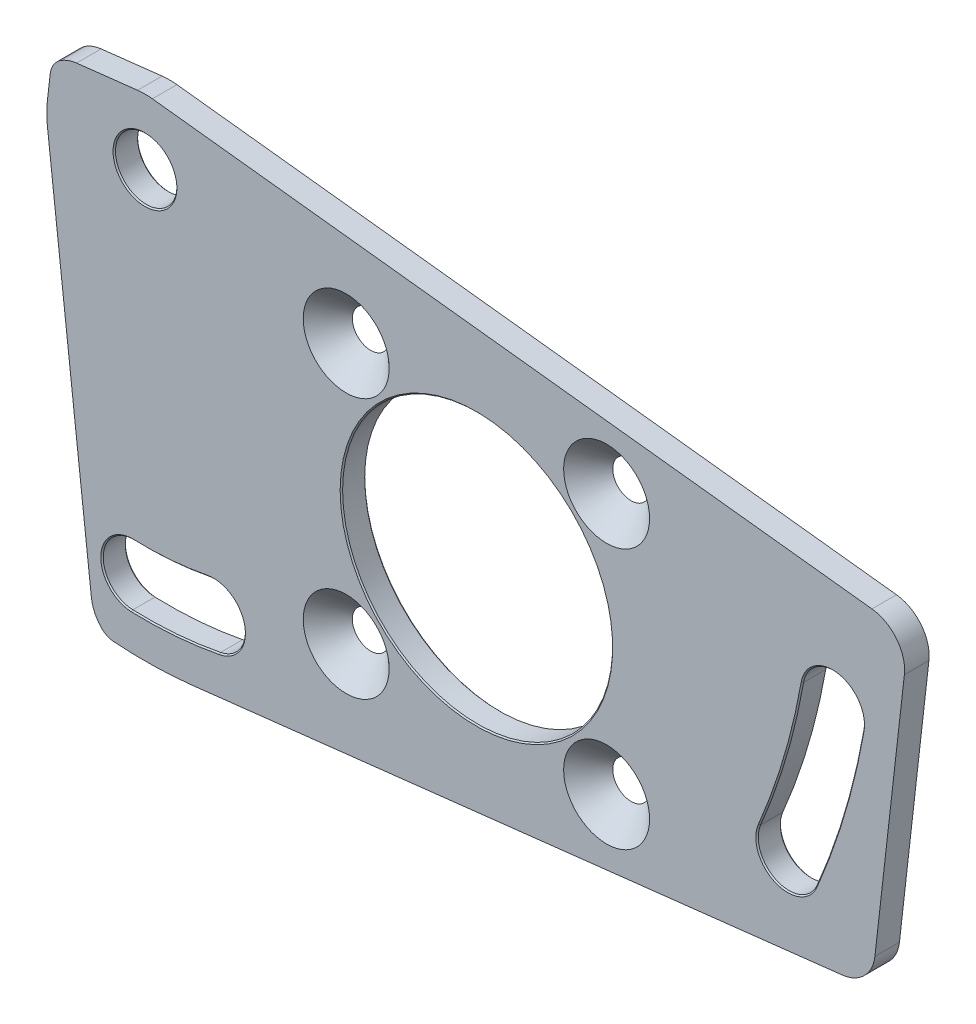
SolidWorks part; units mm, degrees
ref_plane "Płaszczyzna przednia" through (0, 0, 0) normal (0, 0, 1) x (1, 0, 0)
ref_plane "Płaszczyzna górna" through (0, 0, 0) normal (0, 1, 0) x (1, 0, 0)
ref_plane "Płaszczyzna prawa" through (0, 0, 0) normal (1, 0, 0) x (0, 0, -1)
sketch "Szkic1" plane through (0, 0, 0) normal (0, 0, 1) x (1, 0, 0)
  line L0 (25.3611, -7.5593) -> (-27, 14.6667) construction
  line L1 (-32, -20) -> (32, -20)
  line L2 (-35, -17) -> (-35, 17)
  line L3 (-32, 20) -> (32, 20)
  line L4 (35, -17) -> (35, 17)
  line L5 (-35, -20) -> (35, 20) construction
  line L6 (-35, 20) -> (35, -20) construction
  line L7 (-27, 14.6667) -> (29.0188, 4.789) construction
  line L10 (-28, -14.4829) -> (-27, 14.6667) construction
  line L11 (-27, 14.6667) -> (-21.4172, -13.9607) construction
  arc A0 (-32, -20) -> (-35, -17) centre (-32, -17) cw
  arc A1 (32, -20) -> (35, -17) centre (32, -17) ccw
  arc A2 (32, 20) -> (35, 17) centre (32, 17) cw
  arc A3 (-35, 17) -> (-32, 20) centre (-32, 17) cw
  circle A4 centre (0, 0) radius 11
  circle A5 centre (-27, 14.6667) radius 2.5
  arc A6 (25.3611, -7.5593) -> (29.0188, 4.789) centre (-27, 14.6667) ccw construction
  arc A7 (27.6623, -8.5361) -> (31.4808, 4.3549) centre (-27, 14.6667) ccw
  arc A8 (23.0598, -6.5825) -> (26.5568, 5.2232) centre (-27, 14.6667) ccw
  arc A9 (23.0598, -6.5825) -> (27.6623, -8.5361) centre (25.3611, -7.5593) ccw
  arc A10 (31.4808, 4.3549) -> (26.5568, 5.2232) centre (29.0188, 4.789) ccw
  arc A13 (-28, -14.4829) -> (-21.4172, -13.9607) centre (-27, 14.6667) ccw construction
  arc A14 (-28.0857, -16.9814) -> (-20.9386, -16.4145) centre (-27, 14.6667) ccw
  arc A15 (-27.9143, -11.9843) -> (-21.8957, -11.5069) centre (-27, 14.6667) ccw
  arc A16 (-27.9143, -11.9843) -> (-28.0857, -16.9814) centre (-28, -14.4829) ccw
  arc A17 (-20.9386, -16.4145) -> (-21.8957, -11.5069) centre (-21.4172, -13.9607) ccw
  point P0 (0, 0)
  point P25 (27.5405, -1.489)
  point P35 (-24.6938, -14.4087)
  point P36 (27.5405, -1.489)
  dimension "D3" = 3
  dimension "D4" = 5
  dimension "D5" = 22
  dimension "D7" = 2.5
  dimension "D8" = 3
  dimension "D9" = 10
  dimension "D10" = 13
  dimension "D12" = 2.5
  dimension "D11" = 4.5
  dimension "D1" = 70
  dimension "D2" = 40
  dimension "D6" = 13
extrude "Dodanie-wyciągnięcie1" add sketch "Szkic1" along normal blind 2
sketch "Szkic2" plane through (0, 0, 0) normal (0, 0, 1) x (1, 0, 0)
  line L2 (-10.6066, -10.6066) -> (10.6066, -10.6066) construction
  line L3 (-10.6066, -10.6066) -> (-10.6066, 10.6066) construction
  line L4 (-10.6066, 10.6066) -> (10.6066, 10.6066) construction
  line L5 (10.6066, -10.6066) -> (10.6066, 10.6066) construction
  line L6 (-10.6066, -10.6066) -> (10.6066, 10.6066) construction
  line L7 (-10.6066, 10.6066) -> (10.6066, -10.6066) construction
  circle A0 centre (-10.6066, 10.6066) radius 1.5
  circle A1 centre (10.6066, 10.6066) radius 1.5
  circle A2 centre (10.6066, -10.6066) radius 1.5
  circle A3 centre (-10.6066, -10.6066) radius 1.5
  point P11 (0, 0)
  dimension "D1" = 3
  dimension "D2" = 30
extrude "Wytnij-wyciągnięcie2" cut sketch "Szkic2" along normal through all
sketch "Szkic3" plane through (0, 0, 0) normal (0, 0, 1) x (1, 0, 0)
  line L0 (32.4644, -11.109) -> (34.8656, 9.9664)
  line L1 (-34.7231, 17.5512) -> (-34.9486, 15.5723)
  line L2 (32.2245, 13.2867) -> (-26.3962, 19.9657)
  line L9 (-23.0756, -19.7772) -> (29.8233, -13.7501)
  line L11 (-27.6038, 19.9657) -> (-32.5716, 19.3997)
  line L12 (-34.9486, 13.761) -> (-31.3638, -17.7021)
  arc A2 (34.8656, 9.9664) -> (32.2245, 13.2867) centre (31.8849, 10.306) ccw
  arc A4 (-26.3962, 19.9657) -> (-27.6038, 19.9657) centre (-27, 14.6667) ccw
  arc A5 (-33.8699, 18.9324) -> (-34.7231, 17.5512) centre (-32.8292, 17.3354) ccw
  arc A6 (-34.9486, 15.5723) -> (-34.9486, 13.761) centre (-27, 14.6667) ccw
  arc A7 (-29.5516, -19.906) -> (-23.0756, -19.7772) centre (-27, 14.6667) ccw
  arc A8 (-31.3638, -17.7021) -> (-30.5562, -19.4307) centre (-28.3831, -17.3625) ccw
  arc A11 (-32.5716, 19.3997) -> (-33.8699, 18.9324) centre (-32.232, 16.419) ccw
  arc A12 (29.8233, -13.7501) -> (32.4644, -11.109) centre (29.4836, -10.7694) ccw
  arc A13 (-30.5562, -19.4307) -> (-29.5516, -19.906) centre (-29.438, -18.3665) ccw
  point P0 (-27, 14.6667)
  point P1 (-27, 14.6667)
  dimension "D1" = 3
extrude "Wytnij-wyciągnięcie3" cut sketch "Szkic3" along normal through all flip side to cut
chamfer "Sfazowanie1" distance 2 angle 45 4 edges at (-9.1066, -10.6066, 2) (12.1066, -10.6066, 2) (12.1066, 10.6066, 2) (-9.1066, 10.6066, 2)
chamfer "Sfazowanie2" distance 0.1 angle 45 20 edges at (29.9376, -2.199, 2) (29.4529, 7.2511, 2) (24.3842, -9.8605, 2) (25.1435, -0.7789, 2) (29.9376, -2.199, 0) (29.4529, 7.2511, 0) (24.3842, -9.8605, 0) (25.1435, -0.7789, 0) (-24.5, 14.6667, 0) (-24.5, 14.6667, 2) (11, 0, 0) (11, 0, 2) (-18.9634, -13.4822, 2) (-24.8914, -11.9165, 2) (-24.4961, -16.9009, 2) (-30.4985, -14.3971, 2) (-18.9634, -13.4822, 0) (-24.8914, -11.9165, 0) (-24.4961, -16.9009, 0) (-30.4985, -14.3971, 0)
